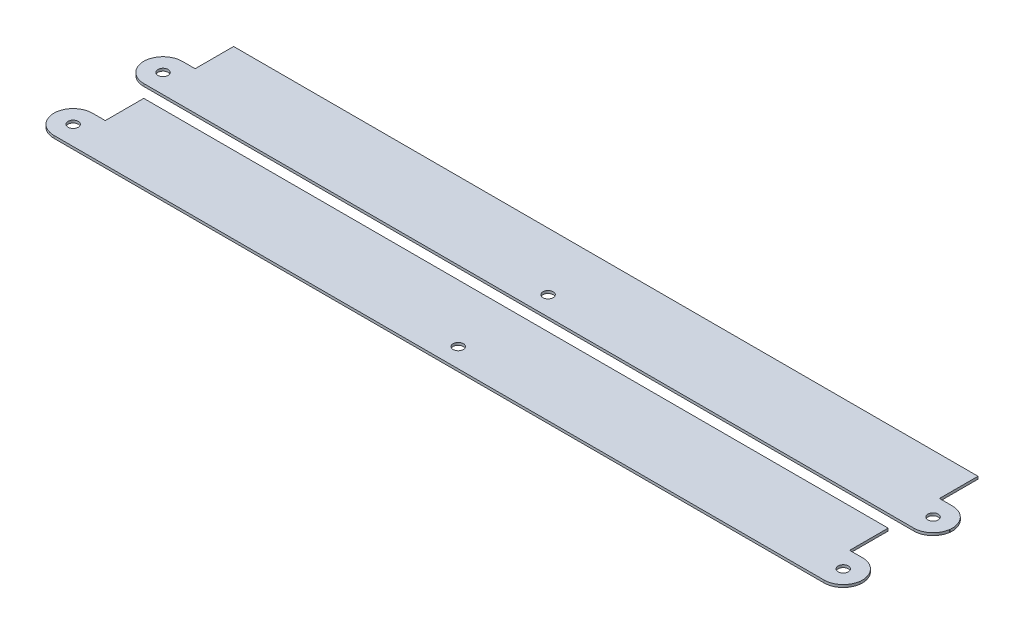
SolidWorks part; units mm, degrees
ref_plane "Front Plane" through (0, 0, 0) normal (0, 0, 1) x (1, 0, 0)
ref_plane "Top Plane" through (0, 0, 0) normal (0, 1, 0) x (1, 0, 0)
ref_plane "Right Plane" through (0, 0, 0) normal (1, 0, 0) x (0, 0, -1)
sketch "Sketch1" plane through (0, 0, 0) normal (0, 1, 0) x (1, 0, 0)
  line L0 (0, 0) -> (300, 0) construction
  line L1 (0, 7.5) -> (5, 7.5)
  line L2 (0, 7.5) -> (300, 7.5) construction
  line L3 (0, 7.5) -> (0, -7.5) construction
  line L4 (0, -7.5) -> (300, -7.5)
  line L5 (300, 7.5) -> (300, -7.5) construction
  line L6 (0, 7.5) -> (300, -7.5) construction
  line L7 (0, -7.5) -> (300, 7.5) construction
  line L8 (5, 7.5) -> (5, 22.5)
  line L9 (5, 22.5) -> (295, 22.5)
  line L10 (295, 22.5) -> (295, 7.5)
  line L11 (295, 7.5) -> (300, 7.5)
  line L17 (300, 0) -> (307.5, 0) construction
  line L19 (307.5, 1) -> (307.5, -1)
  line L20 (307.5, 1) -> (307.433, 1)
  line L21 (307.5, -1) -> (307.433, -1)
  line L32 (-7.5, 1) -> (-7.5, -1)
  line L33 (-7.5, -1) -> (-7.433, -1)
  line L44 (-7.5, 1) -> (-7.433, 1)
  circle A0 centre (0, 0) radius 2
  circle A1 centre (300, 0) radius 2
  arc A2 (0, 7.5) -> (0, -7.5) centre (0, 0) ccw construction
  arc A3 (300, -7.5) -> (300, 7.5) centre (300, 0) ccw construction
  arc A96 (0, 7.5) -> (-7.433, 1) centre (0, 0) ccw
  arc A97 (-7.433, -1) -> (0, -7.5) centre (0, 0) ccw
  arc A98 (307.433, 1) -> (300, 7.5) centre (300, 0) ccw
  arc A99 (307.433, -1) -> (300, -7.5) centre (300, 0) cw
  circle A100 centre (150, 0) radius 2
  point P5 (150, 0)
  point P11 (150, 0)
  point P15 (-7.5, 0)
  dimension "D3" = 15
  dimension "D5" = 4
  dimension "D7" = 2
  dimension "D8" = 4
  dimension "D1" = 2
  dimension "D2" = 5
  dimension "D4" = 15
  dimension "D6" = 300
extrude "Boss-Extrude1" add sketch "Sketch1" along normal blind 1 contours L4 A3 L11 L10 L9 L8 L1 A2 A0 A1 | L9 | L20 L19 L21 | L20 A3 L21 | L20 L21 L19 | A2 L44 L32 L33 region at (150, 0, -7.2588)
pattern_linear "LPattern1" count 2 spacing 35 along (0, 0, -1) of bodies 101
